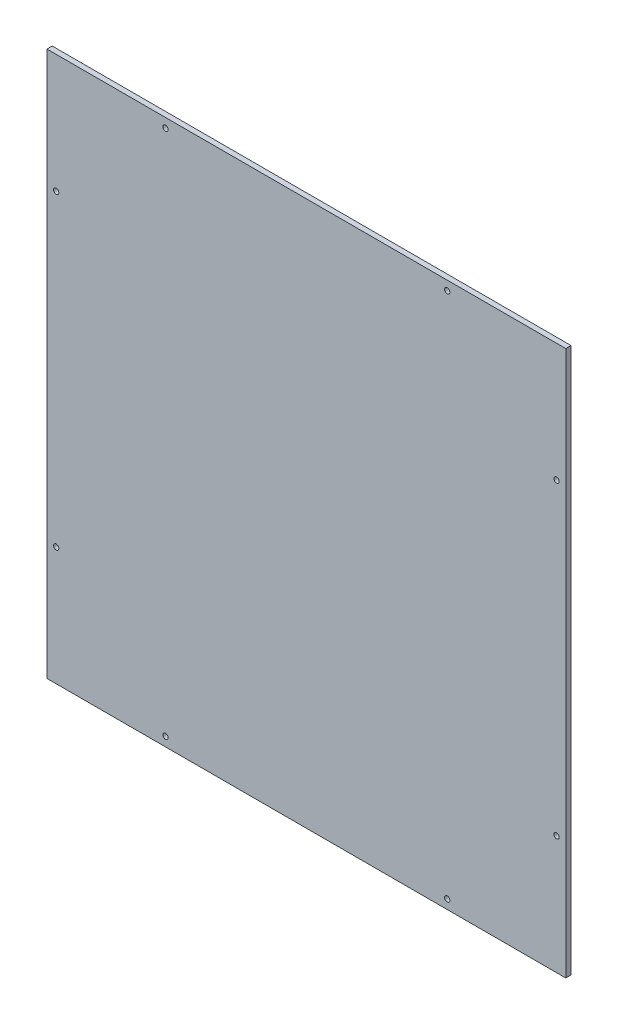
SolidWorks part; units mm, degrees
ref_plane "Piano frontale" through (0, 0, 0) normal (0, 0, 1) x (1, 0, 0)
ref_plane "Piano superiore" through (0, 0, 0) normal (0, 1, 0) x (1, 0, 0)
ref_plane "Piano destro" through (0, 0, 0) normal (1, 0, 0) x (0, 0, -1)
sketch "Schizzo1" plane through (0, 0, 0) normal (0, 0, 1) x (1, 0, 0)
  line L0 (-197, 351.6275) -> (-197, -66.2585) construction
  line L1 (0, 0) -> (-394, 0)
  line L2 (0, 0) -> (0, 414)
  line L3 (0, 414) -> (-394, 414)
  line L4 (-394, 0) -> (-394, 414)
  line L5 (-387.9788, 207) -> (120.8821, 207) construction
  circle A0 centre (-90, 407) radius 2
  circle A1 centre (-7, 324) radius 2
  circle A2 centre (-304, 407) radius 2
  circle A3 centre (-387, 324) radius 2
  circle A4 centre (-304, 7) radius 2
  circle A5 centre (-387, 90) radius 2
  circle A6 centre (-7, 90) radius 2
  circle A7 centre (-90, 7) radius 2
  point P9 (-197, 207)
  dimension "D3" = 4
  dimension "D1" = 394
  dimension "314" = 414
  dimension "D4" = 7
  dimension "D5" = 90
  dimension "D6" = 7
  dimension "D7" = 90
extrude "Estrusione-Estrusione1" add sketch "Schizzo1" along normal blind 4
